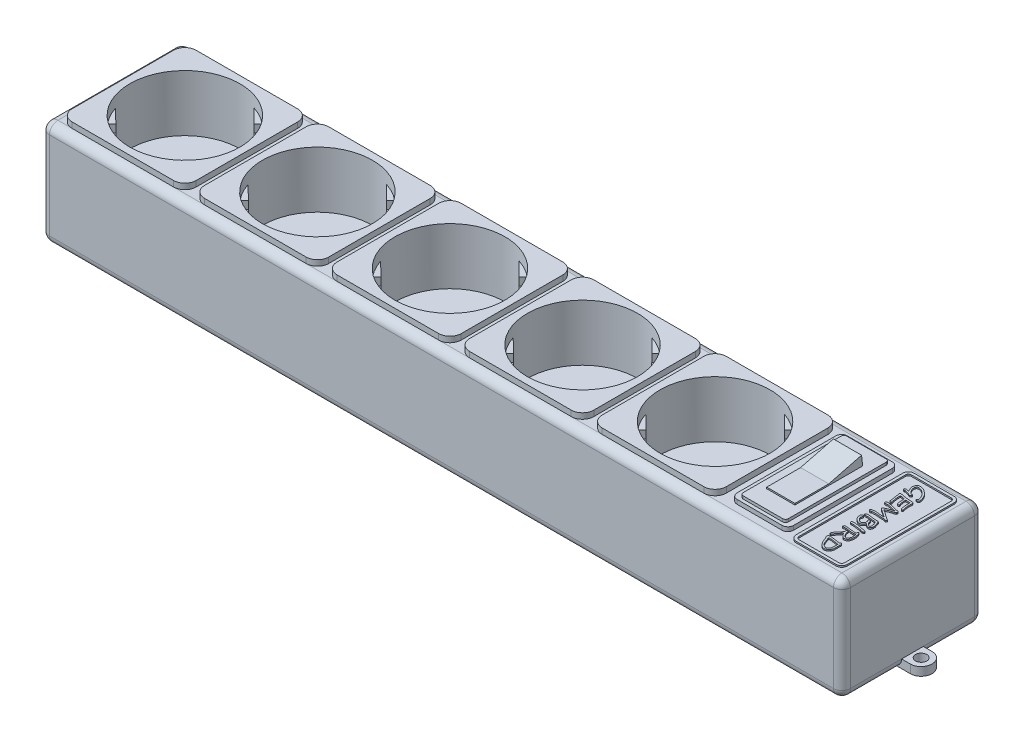
SolidWorks part; units mm, degrees
ref_plane "Front Plane" through (0, 0, 0) normal (0, 0, 1) x (1, 0, 0)
ref_plane "Top Plane" through (0, 0, 0) normal (0, 1, 0) x (1, 0, 0)
ref_plane "Right Plane" through (0, 0, 0) normal (1, 0, 0) x (0, 0, -1)
sketch "Sketch1" plane through (0, 0, 0) normal (0, 1, 0) x (1, 0, 0)
  line L1 (-142, 25) -> (142, 25)
  line L2 (-142, 25) -> (-142, -25)
  line L3 (-142, -25) -> (142, -25)
  line L4 (142, 25) -> (142, -25)
  line L5 (-142, 25) -> (142, -25) construction
  line L6 (-142, -25) -> (142, 25) construction
  point P0 (0, 0)
extrude "Boss-Extrude1" add sketch "Sketch1" along normal blind 39
sketch "Sketch2" plane through (0, 39, 0) normal (0, 1, 0) x (1, 0, 0)
  line L0 (-142, 25) -> (-142, -25) construction
  line L1 (-142, -25) -> (142, -25) construction
  line L2 (-142, 25) -> (142, 25)
  line L3 (-142, 25) -> (-142, -25)
  line L4 (142, 25) -> (-142, 25) construction
  line L5 (-142, -25) -> (142, -25)
  line L6 (142, 25) -> (142, -25)
  line L7 (-134, 22) -> (-98, 22)
  line L8 (-138, 18) -> (-138, -18)
  line L9 (-134, -22) -> (-98, -22)
  line L10 (-94, 18) -> (-94, -18)
  line L11 (-138, 22) -> (-94, -22) construction
  line L12 (-138, -22) -> (-94, 22) construction
  line L13 (-87, 22) -> (-51, 22)
  line L14 (-91, 18) -> (-91, -18)
  line L15 (-87, -22) -> (-51, -22)
  line L16 (-47, 18) -> (-47, -18)
  line L17 (-91, 22) -> (-47, -22) construction
  line L18 (-91, -22) -> (-47, 22) construction
  line L19 (-40, 22) -> (-4, 22)
  line L20 (-44, 18) -> (-44, -18)
  line L21 (-40, -22) -> (-4, -22)
  line L22 (0, 18) -> (0, -18)
  line L23 (-44, 22) -> (0, -22) construction
  line L24 (-44, -22) -> (0, 22) construction
  line L25 (7, 22) -> (43, 22)
  line L26 (3, 18) -> (3, -18)
  line L27 (7, -22) -> (43, -22)
  line L28 (47, 18) -> (47, -18)
  line L29 (3, 22) -> (47, -22) construction
  line L30 (3, -22) -> (47, 22) construction
  line L31 (54, 22) -> (90, 22)
  line L32 (50, 18) -> (50, -18)
  line L33 (54, -22) -> (90, -22)
  line L34 (94, 18) -> (94, -18)
  line L35 (50, 22) -> (94, -22) construction
  line L36 (50, -22) -> (94, 22) construction
  line L37 (142, -25) -> (142, 25) construction
  arc A0 (-134, 22) -> (-138, 18) centre (-134, 18) ccw
  arc A1 (-138, -18) -> (-134, -22) centre (-134, -18) ccw
  arc A2 (-98, -22) -> (-94, -18) centre (-98, -18) ccw
  arc A3 (-98, 22) -> (-94, 18) centre (-98, 18) cw
  arc A4 (-87, 22) -> (-91, 18) centre (-87, 18) ccw
  arc A5 (-91, -18) -> (-87, -22) centre (-87, -18) ccw
  arc A6 (-51, -22) -> (-47, -18) centre (-51, -18) ccw
  arc A7 (-51, 22) -> (-47, 18) centre (-51, 18) cw
  arc A8 (-40, 22) -> (-44, 18) centre (-40, 18) ccw
  arc A9 (-44, -18) -> (-40, -22) centre (-40, -18) ccw
  arc A10 (-4, -22) -> (0, -18) centre (-4, -18) ccw
  arc A11 (-4, 22) -> (0, 18) centre (-4, 18) cw
  arc A12 (7, 22) -> (3, 18) centre (7, 18) ccw
  arc A13 (3, -18) -> (7, -22) centre (7, -18) ccw
  arc A14 (43, -22) -> (47, -18) centre (43, -18) ccw
  arc A15 (43, 22) -> (47, 18) centre (43, 18) cw
  arc A16 (54, 22) -> (50, 18) centre (54, 18) ccw
  arc A17 (50, -18) -> (54, -22) centre (54, -18) ccw
  arc A18 (90, -22) -> (94, -18) centre (90, -18) ccw
  arc A19 (90, 22) -> (94, 18) centre (90, 18) cw
  point P0 (-116, 0)
  point P9 (-116, 0)
  point P31 (-69, 0)
  point P32 (-69, 0)
  point P49 (-22, 0)
  point P50 (-22, 0)
  point P67 (25, 0)
  point P68 (25, 0)
  point P85 (72, 0)
  point P86 (72, 0)
  dimension "D2" = 4
  dimension "D1" = 26
  dimension "D3" = 5
extrude "Cut-Extrude1" cut sketch "Sketch2" against normal blind 2
sketch "Sketch4" plane through (0, 39, 0) normal (0, 1, 0) x (1, 0, 0)
  line L0 (-50.4357, 5.9847) -> (-55.3058, 10.8532)
  line L1 (-97.4357, 5.9847) -> (-102.3058, 10.8532)
  line L2 (-105.1202, 13.6756) -> (-103.6832, 15.1126)
  line L3 (-102.3058, 10.8532) -> (-100.8649, 12.2942)
  line L4 (-58.1202, 13.6756) -> (-56.6832, 15.1126)
  line L5 (-105.1202, 13.6756) -> (-109.9832, 18.5386)
  line L6 (-129.6513, -10.8264) -> (-134.5335, -6.0468)
  line L7 (-126.8175, -13.6627) -> (-128.2953, -15.1405)
  line L8 (-129.6513, -10.8264) -> (-131.129, -12.3042)
  line L9 (-122.0359, -18.5522) -> (-126.8175, -13.6627)
  line L10 (-55.3058, 10.8532) -> (-53.8649, 12.2942)
  line L11 (-58.1202, 13.6756) -> (-62.9832, 18.5386)
  line L12 (-82.6513, -10.8264) -> (-87.5335, -6.0468)
  line L13 (-79.8175, -13.6627) -> (-81.2953, -15.1405)
  line L14 (-82.6513, -10.8264) -> (-84.129, -12.3042)
  line L15 (-75.0359, -18.5522) -> (-79.8175, -13.6627)
  line L16 (-3.4357, 5.9847) -> (-8.3058, 10.8532)
  line L17 (-11.1202, 13.6756) -> (-9.6832, 15.1126)
  line L18 (-8.3058, 10.8532) -> (-6.8649, 12.2942)
  line L19 (-11.1202, 13.6756) -> (-15.9832, 18.5386)
  line L20 (-35.6513, -10.8264) -> (-40.5335, -6.0468)
  line L21 (-32.8175, -13.6627) -> (-34.2953, -15.1405)
  line L22 (-35.6513, -10.8264) -> (-37.129, -12.3042)
  line L23 (-28.0359, -18.5522) -> (-32.8175, -13.6627)
  line L24 (43.5643, 5.9847) -> (38.6942, 10.8532)
  line L25 (35.8798, 13.6756) -> (37.3168, 15.1126)
  line L26 (38.6942, 10.8532) -> (40.1351, 12.2942)
  line L27 (35.8798, 13.6756) -> (31.0168, 18.5386)
  line L28 (11.3487, -10.8264) -> (6.4665, -6.0468)
  line L29 (14.1825, -13.6627) -> (12.7047, -15.1405)
  line L30 (11.3487, -10.8264) -> (9.871, -12.3042)
  line L31 (18.9641, -18.5522) -> (14.1825, -13.6627)
  line L32 (90.5643, 5.9847) -> (85.6942, 10.8532)
  line L33 (82.8798, 13.6756) -> (84.3168, 15.1126)
  line L34 (85.6942, 10.8532) -> (87.1351, 12.2942)
  line L35 (82.8798, 13.6756) -> (78.0168, 18.5386)
  line L36 (58.3487, -10.8264) -> (53.4665, -6.0468)
  line L37 (61.1825, -13.6627) -> (59.7047, -15.1405)
  line L38 (58.3487, -10.8264) -> (56.871, -12.3042)
  line L39 (65.9641, -18.5522) -> (61.1825, -13.6627)
  arc A0 (-131.129, -12.3042) -> (-128.2953, -15.1405) centre (-115.9904, -0.013) ccw
  arc A1 (-109.9832, 18.5386) -> (-134.5335, -6.0468) centre (-115.9904, -0.013) ccw
  arc A2 (-84.129, -12.3042) -> (-81.2953, -15.1405) centre (-68.9904, -0.013) ccw
  arc A3 (-100.8649, 12.2942) -> (-103.6832, 15.1126) centre (-115.9904, -0.013) ccw
  arc A4 (-122.0359, -18.5522) -> (-97.4357, 5.9847) centre (-115.9904, -0.013) ccw
  arc A5 (-62.9832, 18.5386) -> (-87.5335, -6.0468) centre (-68.9904, -0.013) ccw
  arc A6 (-53.8649, 12.2942) -> (-56.6832, 15.1126) centre (-68.9904, -0.013) ccw
  arc A7 (-75.0359, -18.5522) -> (-50.4357, 5.9847) centre (-68.9904, -0.013) ccw
  arc A8 (-37.129, -12.3042) -> (-34.2953, -15.1405) centre (-21.9904, -0.013) ccw
  arc A9 (-15.9832, 18.5386) -> (-40.5335, -6.0468) centre (-21.9904, -0.013) ccw
  arc A10 (-6.8649, 12.2942) -> (-9.6832, 15.1126) centre (-21.9904, -0.013) ccw
  arc A11 (-28.0359, -18.5522) -> (-3.4357, 5.9847) centre (-21.9904, -0.013) ccw
  arc A12 (9.871, -12.3042) -> (12.7047, -15.1405) centre (25.0096, -0.013) ccw
  arc A13 (31.0168, 18.5386) -> (6.4665, -6.0468) centre (25.0096, -0.013) ccw
  arc A14 (40.1351, 12.2942) -> (37.3168, 15.1126) centre (25.0096, -0.013) ccw
  arc A15 (18.9641, -18.5522) -> (43.5643, 5.9847) centre (25.0096, -0.013) ccw
  arc A16 (56.871, -12.3042) -> (59.7047, -15.1405) centre (72.0096, -0.013) ccw
  arc A17 (78.0168, 18.5386) -> (53.4665, -6.0468) centre (72.0096, -0.013) ccw
  arc A18 (87.1351, 12.2942) -> (84.3168, 15.1126) centre (72.0096, -0.013) ccw
  arc A19 (65.9641, -18.5522) -> (90.5643, 5.9847) centre (72.0096, -0.013) ccw
extrude "Cut-Extrude4" cut sketch "Sketch4" against normal blind 20
sketch "Sketch3" plane through (0, 39, 0) normal (0, 1, 0) x (1, 0, 0)
  circle A0 centre (-115.9904, -0.013) radius 19.5
  circle A1 centre (-68.9904, -0.013) radius 19.5
  circle A2 centre (-21.9904, -0.013) radius 19.5
  circle A3 centre (25.0096, -0.013) radius 19.5
  circle A4 centre (72.0096, -0.013) radius 19.5
extrude "Cut-Extrude7" cut sketch "Sketch3" against normal blind 4
sketch "Sketch5" plane through (0, 19, 0) normal (0, 1, 0) x (1, 0, 0)
  line L0 (-102.2019, 13.7756) -> (-129.7853, -13.7953) construction
  line L1 (-136.8284, 20.8284) -> (-95.1716, -20.8284) construction
  circle A4 centre (-109.2728, 6.7078) radius 2.5
  circle A5 centre (-122.7078, -6.7272) radius 2.5
  circle A6 centre (-62.2728, 6.7078) radius 2.5
  circle A7 centre (-75.7078, -6.7272) radius 2.5
  circle A8 centre (-15.2728, 6.7078) radius 2.5
  circle A9 centre (-28.7078, -6.7272) radius 2.5
  circle A10 centre (31.7272, 6.7078) radius 2.5
  circle A11 centre (18.2922, -6.7272) radius 2.5
  circle A12 centre (78.7272, 6.7078) radius 2.5
  circle A13 centre (65.2922, -6.7272) radius 2.5
  dimension "D1" = 9.5
extrude "Cut-Extrude8" cut sketch "Sketch5" against normal blind 17
sketch "Sketch6" plane through (0, 0, 0) normal (0, -1, 0) x (1, 0, 0)
  line L0 (0, 25) -> (0, 96.2198) construction
  line L1 (-142, -3.8452) -> (-145.0817, -3.8452)
  line L2 (-142, 3.8452) -> (-145.0817, 3.8452)
  line L3 (-142, 3.8452) -> (-142, -3.8452)
  line L4 (-142, -25) -> (-142, 25) construction
  line L6 (142, 3.8452) -> (142, -3.8452)
  line L7 (142, 3.8452) -> (145.0817, 3.8452)
  line L8 (142, -3.8452) -> (145.0817, -3.8452)
  circle A0 centre (-145.0817, 0) radius 2
  arc A1 (-145.0817, 3.8452) -> (-145.0817, -3.8452) centre (-145.0817, 0) ccw
  arc A2 (145.0817, 3.8452) -> (145.0817, -3.8452) centre (145.0817, 0) cw
  circle A3 centre (145.0817, 0) radius 2
extrude "Boss-Extrude2" add sketch "Sketch6" against normal blind 3
fillet "Fillet1" radius 3 14 edges at (142, 18.5, 25) (142, 18.5, -25) (-142, 18.5, 25) (-142, 18.5, -25) (0, 0, -25) (0, 0, 25) (0, 37, 25) (-142, 37, 0) (0, 37, -25) (142, 37, 0)
sketch "Sketch7" plane through (0, 37, 0) normal (0, 1, 0) x (1, 0, 0)
  line L1 (99.3242, 19.5234) -> (115.3242, 19.5234)
  line L2 (97.3242, 17.5234) -> (97.3242, -17.5234)
  line L3 (99.3242, -19.5234) -> (115.3242, -19.5234)
  line L4 (117.3242, 17.5234) -> (117.3242, -17.5234)
  line L5 (97.3242, 19.5234) -> (117.3242, -19.5234) construction
  line L6 (97.3242, -19.5234) -> (117.3242, 19.5234) construction
  arc A0 (97.3242, -17.5234) -> (99.3242, -19.5234) centre (99.3242, -17.5234) ccw
  arc A1 (115.3242, -19.5234) -> (117.3242, -17.5234) centre (115.3242, -17.5234) ccw
  arc A2 (117.3242, 17.5234) -> (115.3242, 19.5234) centre (115.3242, 17.5234) ccw
  arc A3 (99.3242, 19.5234) -> (97.3242, 17.5234) centre (99.3242, 17.5234) ccw
  point P0 (107.3242, 0)
  dimension "D1" = 2
extrude "Boss-Extrude3" add sketch "Sketch7" along normal blind 1.5
sketch "Sketch8" plane through (0, 38.5, 0) normal (0, 1, 0) x (1, 0, 0)
  line L1 (100.3242, 18.3451) -> (114.3242, 18.3451)
  line L2 (99.3242, 17.3451) -> (99.3242, -17.3451)
  line L3 (100.3242, -18.3451) -> (114.3242, -18.3451)
  line L4 (115.3242, 17.3451) -> (115.3242, -17.3451)
  line L5 (99.3242, 18.3451) -> (115.3242, -18.3451) construction
  line L6 (99.3242, -18.3451) -> (115.3242, 18.3451) construction
  arc A0 (99.3242, -17.3451) -> (100.3242, -18.3451) centre (100.3242, -17.3451) ccw
  arc A1 (114.3242, -18.3451) -> (115.3242, -17.3451) centre (114.3242, -17.3451) ccw
  arc A2 (115.3242, 17.3451) -> (114.3242, 18.3451) centre (114.3242, 17.3451) ccw
  arc A3 (100.3242, 18.3451) -> (99.3242, 17.3451) centre (100.3242, 17.3451) ccw
  point P0 (107.3242, 0)
  dimension "D1" = 1
extrude "Boss-Extrude4" add sketch "Sketch8" along normal blind 1
ref_plane "Plane1" through (107.3242, 0, 0) normal (1, 0, 0) x (0, 0, -1)
sketch "Sketch9" plane through (107.3242, 0, 0) normal (1, 0, 0) x (0, 0, -1)
  line L0 (0, 39.5) -> (0, 51.0408) construction
  line L1 (12, 39.5) -> (11.6218, 42.9961)
  line L2 (0, 40.0071) -> (-12, 40.0071)
  line L3 (-12, 40.0071) -> (-12, 39.5)
  line L4 (-17.3451, 39.5) -> (17.3451, 39.5) construction
  line L5 (-12, 39.5) -> (12, 39.5)
  line L6 (0, 40.0071) -> (11.6218, 42.9961)
extrude "Boss-Extrude5" add sketch "Sketch9" along normal mid plane 10
sketch "Sketch10" plane through (0, 37, 0) normal (0, 1, 0) x (1, 0, 0)
  line L0 (121.6582, 19.9157) -> (135.8345, 19.9157)
  line L1 (121.6582, 20.9157) -> (135.8345, 20.9157)
  line L2 (119.6582, 18.9157) -> (119.6582, -18.9157)
  line L3 (121.6582, -20.9157) -> (135.8345, -20.9157)
  line L4 (137.8345, 18.9157) -> (137.8345, -18.9157)
  line L5 (125.4661, -19.9157) -> (125.4661, 41.0908) construction
  line L7 (136.8345, 18.9157) -> (136.8345, -18.9157)
  line L8 (121.6582, -19.9157) -> (135.8345, -19.9157)
  line L9 (120.6582, 18.9157) -> (120.6582, -18.9157)
  arc A0 (119.6582, -18.9157) -> (121.6582, -20.9157) centre (121.6582, -18.9157) ccw
  arc A1 (135.8345, -20.9157) -> (137.8345, -18.9157) centre (135.8345, -18.9157) ccw
  arc A2 (137.8345, 18.9157) -> (135.8345, 20.9157) centre (135.8345, 18.9157) ccw
  arc A3 (121.6582, 20.9157) -> (119.6582, 18.9157) centre (121.6582, 18.9157) ccw
  arc A4 (136.8345, 18.9157) -> (135.8345, 19.9157) centre (135.8345, 18.9157) ccw
  arc A5 (135.8345, -19.9157) -> (136.8345, -18.9157) centre (135.8345, -18.9157) ccw
  arc A6 (120.6582, -18.9157) -> (121.6582, -19.9157) centre (121.6582, -18.9157) ccw
  arc A7 (121.6582, 19.9157) -> (120.6582, 18.9157) centre (121.6582, 18.9157) ccw
  point P0 (128.7463, 0)
  dimension "D1" = 2
  dimension "D2" = 1
extrude "Boss-Extrude6" add sketch "Sketch10" along normal blind 0.5
sketch "Sketch12" plane through (0, 37, 0) normal (0, 1, 0) x (1, 0, 0)
  line L0 (125.4251, 19.9157) -> (125.4251, 10.3281) construction
  text T0 "           GEMBIRD" font "Segoe Script" height in points 21
extrude "Boss-Extrude7" add sketch "Sketch12" along normal blind 0.5
